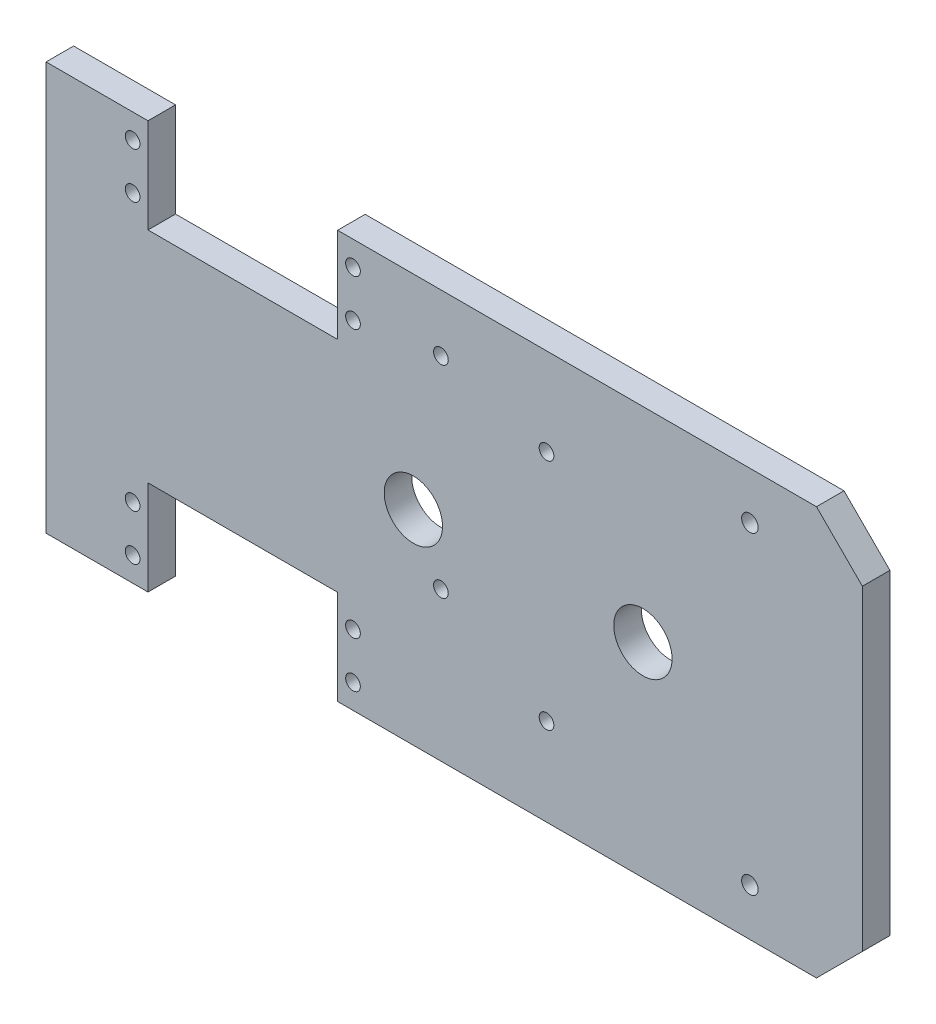
SolidWorks part; units mm, degrees
ref_plane "Front Plane" through (0, 0, 0) normal (0, 0, 1) x (1, 0, 0)
ref_plane "Top Plane" through (0, 0, 0) normal (0, 1, 0) x (1, 0, 0)
ref_plane "Right Plane" through (0, 0, 0) normal (1, 0, 0) x (0, 0, -1)
sketch "Sketch1" plane through (0, 0, 0) normal (0, 0, 1) x (1, 0, 0)
  line L0 (0, -44.45) -> (22.2, -44.45)
  line L1 (22.2, -44.45) -> (22.2, -23.85)
  line L2 (22.2, -23.85) -> (63.5, -23.85)
  line L3 (63.5, -23.85) -> (63.5, -44.45)
  line L4 (63.5, -44.45) -> (167.8, -44.45)
  line L5 (167.8, -44.45) -> (177.8, -34.45)
  line L6 (177.8, -34.45) -> (177.8, 34.45)
  line L7 (177.8, 34.45) -> (167.8, 44.45)
  line L8 (167.8, 44.45) -> (63.5, 44.45)
  line L9 (63.5, 44.45) -> (63.5, 23.85)
  line L10 (63.5, 23.85) -> (22.2, 23.85)
  line L11 (22.2, 23.85) -> (22.2, 44.45)
  line L12 (22.2, 44.45) -> (0, 44.45)
  line L13 (0, 44.45) -> (0, -44.45)
  circle A0 centre (18.85, 29.15) radius 1.6
  circle A1 centre (18.85, 39.15) radius 1.6
  circle A2 centre (66.85, 29.15) radius 1.6
  circle A3 centre (66.85, 39.15) radius 1.6
  circle A4 centre (153.3, 34.15) radius 1.8
  circle A5 centre (109, 25.4) radius 1.6
  circle A6 centre (18.85, -29.15) radius 1.6
  circle A7 centre (18.85, -39.15) radius 1.6
  circle A8 centre (66.85, -29.15) radius 1.6
  circle A9 centre (66.85, -39.15) radius 1.6
  circle A10 centre (153.3, -34.15) radius 1.8
  circle A11 centre (109, -25.4) radius 1.6
  circle A12 centre (86, -12) radius 1.6
  circle A13 centre (86, 32) radius 1.6
  circle A14 centre (80, 0) radius 6.35
  circle A15 centre (130, 0) radius 6.35
extrude "Boss-Extrude1" add sketch "Sketch1" along normal blind 6
ref_plane "LegPlane" through (0, 0, 23) normal (0, 0, 1) x (1, 0, 0)
ref_plane "LinkPlane" through (0, 0, 35.35) normal (0, 0, 1) x (1, 0, 0)
ref_plane "FrontPivot_R_px" through (153.3, 0, 0) normal (1, 0, 0) x (0, 0, -1)
ref_plane "FrontPivot_R_py" through (0, -34.15, 0) normal (0, 1, 0) x (1, 0, 0)
ref_axis "FrontPivot_R" through (153.3, -34.15, 6.3) along (0, 0, -1)
ref_plane "FrontPivot_L_px" through (153.3, 0, 0) normal (1, 0, 0) x (0, 0, -1)
ref_plane "FrontPivot_L_py" through (0, 34.15, 0) normal (0, 1, 0) x (1, 0, 0)
ref_axis "FrontPivot_L" through (153.3, 34.15, 6.3) along (0, 0, -1)
